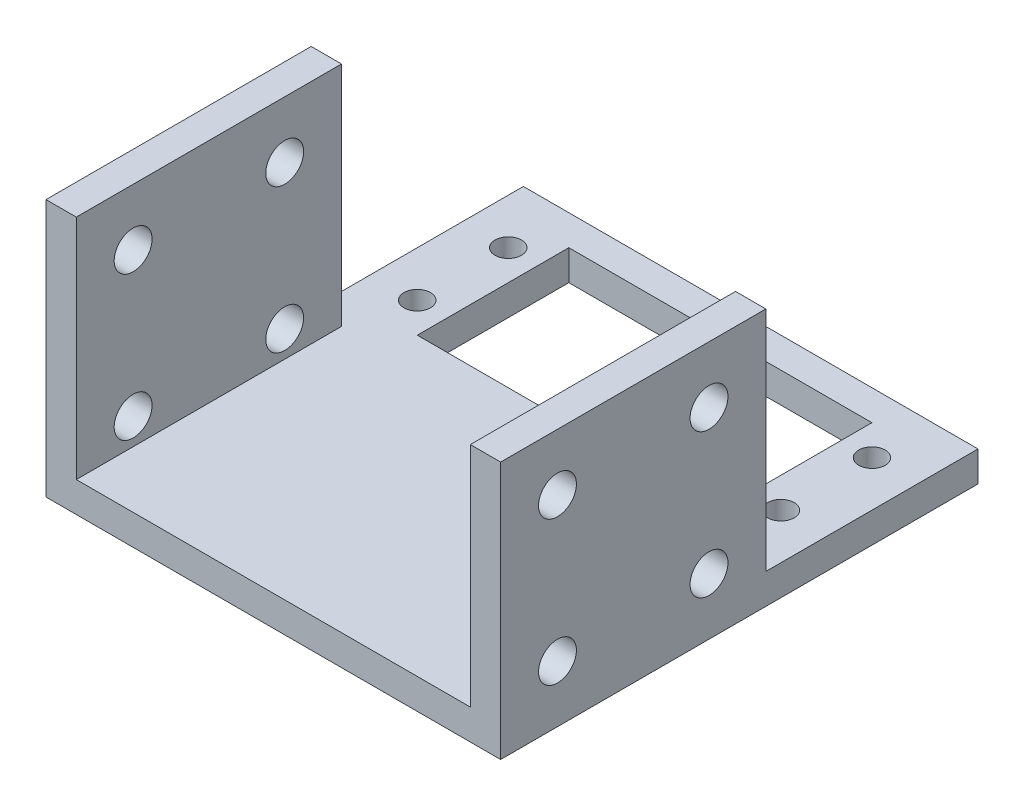
SolidWorks part; units mm, degrees
ref_plane "前视基准面" through (0, 0, 0) normal (0, 0, 1) x (1, 0, 0)
ref_plane "上视基准面" through (0, 0, 0) normal (0, 1, 0) x (1, 0, 0)
ref_plane "右视基准面" through (0, 0, 0) normal (1, 0, 0) x (0, 0, -1)
other "Configuration Table"
sketch "草图1" plane through (0, 0, 0) normal (0, 1, 0) x (1, 0, 0)
  line L0 (0, 0) -> (-40.4808, 0) construction
  line L1 (-20, -10) -> (20, -10)
  line L2 (-20, -10) -> (-20, 10)
  line L3 (-20, 10) -> (20, 10)
  line L4 (20, -10) -> (20, 10)
  line L5 (-20, -10) -> (20, 10) construction
  line L6 (-20, 10) -> (20, -10) construction
  line L7 (-30, 14) -> (30, 14)
  line L8 (-30, 14) -> (-30, -14)
  line L9 (-30, -14) -> (30, -14)
  line L10 (30, 14) -> (30, -14)
  line L11 (-30, 14) -> (30, -14) construction
  line L12 (-30, -14) -> (30, 14) construction
  line L13 (0, 14) -> (0, -14) construction
  line L15 (-30, -14) -> (30, -14)
  line L16 (-30, -14) -> (-30, -49)
  line L17 (-30, -49) -> (30, -49)
  line L18 (30, -14) -> (30, -49)
  line L19 (-30, -14) -> (-26, -14)
  line L20 (-30, -14) -> (-30, -49)
  line L21 (-30, -49) -> (-26, -49)
  line L22 (-26, -14) -> (-26, -49)
  line L23 (30, -14) -> (26, -14)
  line L24 (30, -14) -> (30, -49)
  line L25 (30, -49) -> (26, -49)
  line L26 (26, -14) -> (26, -49)
  circle A0 centre (-24, 6.0071) radius 1.75
  circle A1 centre (-24, -6.0071) radius 1.75
  circle A2 centre (24, -6.0071) radius 1.75
  circle A3 centre (24, 6.0071) radius 1.75
  point P0 (0, 0)
  point P6 (0, 0)
  dimension "D5" = 3.5
  dimension "D7" = 35
  dimension "D1" = 40
  dimension "D2" = 20
  dimension "D3" = 4
  dimension "D4" = 10
  dimension "D6" = 4
  dimension "D8" = 4
  dimension "D9" = 4
extrude "凸台-拉伸1" add sketch "草图1" along normal blind 4 contours L26 L15 L22 L17 | L10 L7 L8 L9 L15 A1 A0 L4 L1 L2 L3 A2 A3 region at (0, 0, -13.3379) region at (0, 0, 31.5)
extrude "凸台-拉伸2" add sketch "草图1<3>" along normal blind 34 contours L9 L26 L17 L18 | L22 L9 L16 L17 region at (-28, 0, 31.5) region at (28, 0, 31.5)
sketch "草图1<3>" plane through (0, 0, 0) normal (0, 1, 0) x (1, 0, 0) same geometry as "草图1"
sketch "草图2" plane through (30, 0, 0) normal (1, 0, 0) x (0, 0, -1)
  line L1 (-14, 34) -> (-49, 34) construction
  line L2 (-49, 34) -> (-49, 0) construction
  line L3 (-14, 34) -> (-14, 4) construction
  line L4 (14, 0) -> (-49, 0) construction
  line L5 (14, 4) -> (-14, 4) construction
  circle A0 centre (-41.5, 26.5) radius 2.5
  circle A1 centre (-21.5, 26.5) radius 2.5
  circle A2 centre (-21.5, 7.5) radius 2.5
  circle A3 centre (-41.5, 7.5) radius 2.5
  dimension "D1" = 5
  dimension "D2" = 5
  dimension "D3" = 5
  dimension "D4" = 5
  dimension "D6" = 7.5
  dimension "D7" = 7.5
  dimension "D10" = 7.5
  dimension "D11" = 7.5
  dimension "D5" = 7.5
  dimension "D8" = 7.5
  dimension "D9" = 7.5
  dimension "D12" = 7.5
extrude "切除-拉伸1" cut sketch "草图2" against normal through all
